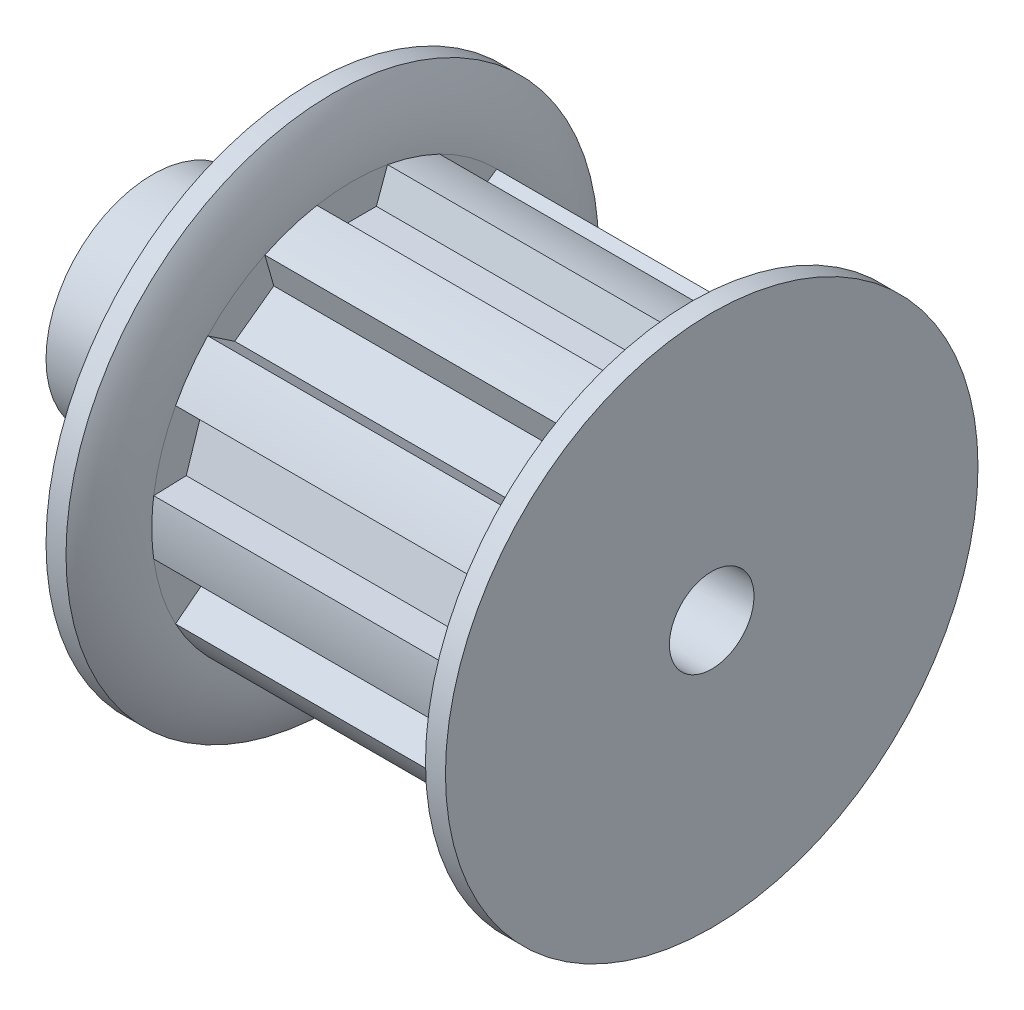
SolidWorks part; units mm, degrees
ref_plane "Front Plane" through (0, 0, 0) normal (0, 0, 1) x (1, 0, 0)
ref_plane "Top Plane" through (0, 0, 0) normal (0, 1, 0) x (1, 0, 0)
ref_plane "Right Plane" through (0, 0, 0) normal (1, 0, 0) x (0, 0, -1)
sketch "Sketch1" plane through (0, 0, 0) normal (1, 0, 0) x (0, 0, -1)
  line L3 (0, 0) -> (0, 6.325) construction
  line L6 (0, 6.325) -> (0, 7.525) construction
  line L7 (-1.325, 7.4074) -> (-0.9072, 6.2596)
  line L8 (1.325, 7.4074) -> (0.9072, 6.2596)
  line L9 (0, -2.2) -> (0, -3.2) construction
  line L10 (0, 8.025) -> (0, 7.525) construction
  line L12 (-0.9072, 6.2596) -> (0.9072, 6.2596)
  line L15 (0, 0) -> (0, -2.2) construction
  circle A0 centre (0, 0) radius 8.025 construction
  circle A1 centre (0, 0) radius 6.325 construction
  arc A7 (1.325, 7.4074) -> (-1.325, 7.4074) centre (0, 0) ccw
  dimension "PD" = 16.05
  dimension "D1" = 40
  dimension "D3" = 0.5
  dimension "D2" = 1.2
  dimension "D4" = 2.65
sketch "Sketch2" plane through (0, 0, 0) normal (0, 0, 1) x (1, 0, 0)
  line L0 (-10.5, 0) -> (10.5, 0) construction
  line L1 (-10.5, 2) -> (10.5, 2)
  line L2 (-10.5, 2) -> (-10.5, 4)
  line L3 (-4.5, 10) -> (-3.75, 10)
  line L4 (-3, 7.525) -> (-4.5, 7.525) construction
  line L5 (9.75, 7.525) -> (9.75, 10) construction
  line L6 (-3, 7.525) -> (9, 7.525)
  line L8 (9, 7.525) -> (10.5, 7.525) construction
  line L9 (9.75, 10) -> (10.5, 10)
  line L10 (10.5, 10) -> (10.5, 2)
  line L12 (-7.5, 4) -> (-7.5, 2) construction
  line L13 (-4.5, 10) -> (-4.5, 4)
  line L14 (-4.5, 4) -> (-10.5, 4)
  arc A0 (9, 7.525) -> (9.75, 10) centre (13.4588, 7.525) cw
  arc A1 (-3, 7.525) -> (-3.75, 10) centre (-7.4588, 7.525) ccw
  point P19 (-3, 7.525)
  point P20 (9, 7.525)
  dimension "Bore Size" = 4
  dimension "Overall Width" = 21
  dimension "Inside Width" = 12
  dimension "Outside Width" = 15
  dimension "Hub Dia" = 8
  dimension "OD" = 20
sketch "Sketch6" plane through (0, 0, 0) normal (0, 0, 1) x (1, 0, 0)
  line L0 (9.75, 10) -> (10.5, 10) construction
  line L1 (-3, 7.525) -> (9, 7.525) construction
  line L2 (-4.5, 10) -> (-3.75, 10) construction
  line L3 (-4.5, 10) -> (-4.5, 4) construction
  line L4 (-4.5, 4) -> (-10.5, 4) construction
  line L5 (-10.5, 2) -> (-10.5, 4) construction
  line L6 (-10.5, 2) -> (10.5, 2) construction
  line L7 (10.5, 10) -> (10.5, 2) construction
  line L8 (9.75, 10) -> (10.5, 10)
  line L9 (-3, 7.525) -> (9, 7.525)
  line L10 (-4.5, 10) -> (-3.75, 10)
  line L11 (-4.5, 10) -> (-4.5, 4)
  line L12 (-4.5, 4) -> (-10.5, 4)
  line L13 (-10.5, 2) -> (-10.5, 4)
  line L14 (-10.5, 2) -> (10.5, 2)
  line L15 (10.5, 10) -> (10.5, 2)
  arc A0 (9.75, 10) -> (9, 7.525) centre (13.4588, 7.525) ccw construction
  arc A1 (-3, 7.525) -> (-3.75, 10) centre (-7.4588, 7.525) ccw construction
  arc A2 (9.75, 10) -> (9, 7.525) centre (13.4588, 7.525) ccw
  arc A3 (-3, 7.525) -> (-3.75, 10) centre (-7.4588, 7.525) ccw
revolve "Revolve1" add sketch "Sketch6" angle 360 about L0
sketch "Sketch3" plane through (0, 0, 0) normal (1, 0, 0) x (0, 0, -1)
  line L2 (-1.325, 7.4074) -> (-0.9072, 6.2596) construction
  line L3 (-0.9072, 6.2596) -> (0.9072, 6.2596) construction
  line L4 (1.325, 7.4074) -> (0.9072, 6.2596) construction
  line L5 (-1.325, 7.4074) -> (-0.9072, 6.2596)
  line L6 (-0.9072, 6.2596) -> (0.9072, 6.2596)
  line L7 (1.325, 7.4074) -> (0.9072, 6.2596)
  arc A1 (1.325, 7.4074) -> (-1.325, 7.4074) centre (0, 0) ccw construction
  arc A2 (1.325, 7.4074) -> (-1.325, 7.4074) centre (0, 0) ccw
extrude "Cut-Extrude1" cut sketch "Sketch3" along normal up to vertex (9 mm away) from vertex up to point (9, 7.525, 0) starting at point (-3, 7.525, 0)
pattern_circular "CirPattern1" count 10 over 360 about axis through (-10.5, 0, 0) along (-1, 0, 0) of "Cut-Extrude1"
sketch "Sketch5" plane through (0, 0, 0) normal (0, 0, 1) x (1, 0, 0)
  line L0 (-10.5, 0) -> (10.5, 0) construction
  point P0 (9, 0)
ref_axis "Center Axis 1" through (10.5, 0, 0) along (-1, 0, 0)
sketch "Sketch7" plane through (0, 0, 0) normal (1, 0, 0) x (0, 0, -1)
  circle A0 centre (0, 0) radius 1.5875
  circle A1 centre (0, 0) radius 2.3835
  dimension "D1" = 3.175
extrude "Boss-Extrude1" add sketch "Sketch7" against normal up to surface (10.5 mm away) from surface up to face at (-10.5, 0, 2) starting at face at (10.5, 0, 10)
equation "\"D3@Sketch1\" = \"ht@Sketch1\" / 2"
equation "\"D2@Sketch1\" = \"hs@Sketch1\" - \"ht@Sketch1\""
